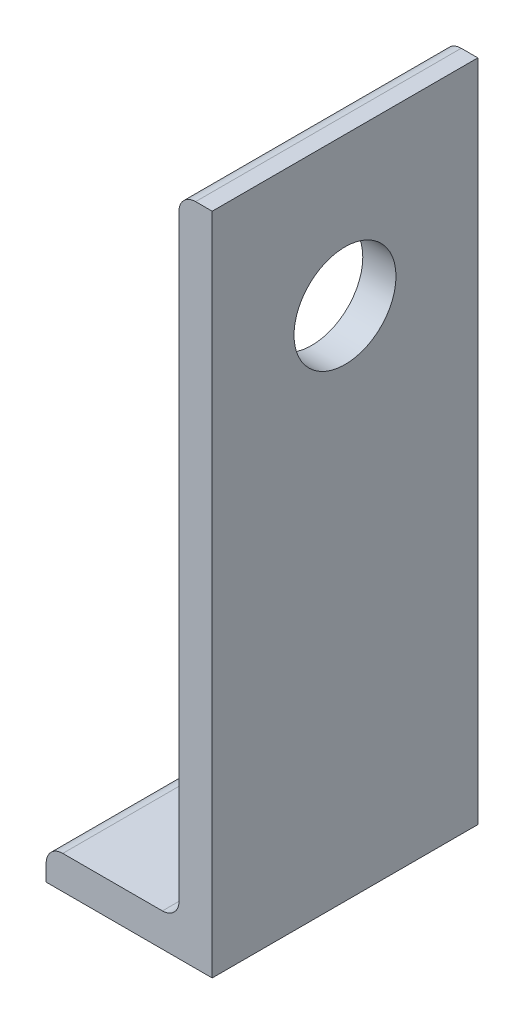
SolidWorks part; units mm, degrees
ref_plane "Front Plane" through (0, 0, 0) normal (0, 0, 1) x (1, 0, 0)
ref_plane "Top Plane" through (0, 0, 0) normal (0, 1, 0) x (1, 0, 0)
ref_plane "Right Plane" through (0, 0, 0) normal (1, 0, 0) x (0, 0, -1)
sketch "Sketch2" plane through (0, 0, 0) normal (0, 0, 1) x (1, 0, 0)
  line L0 (-15.875, 0) -> (15.875, 0)
  line L1 (15.875, 0) -> (15.875, 127)
  line L2 (15.875, 127) -> (9.525, 127) construction
  line L3 (9.525, 123.825) -> (9.525, 9.525)
  line L4 (6.35, 6.35) -> (-12.7, 6.35)
  line L5 (-15.875, 0) -> (-15.875, 6.35) construction
  line L6 (12.7, 127) -> (15.875, 127)
  line L7 (-15.875, 3.175) -> (-15.875, 0)
  arc A0 (9.525, 123.825) -> (12.7, 127) centre (12.7, 123.825) cw
  arc A1 (-15.875, 3.175) -> (-12.7, 6.35) centre (-12.7, 3.175) cw
  arc A2 (9.525, 9.525) -> (6.35, 6.35) centre (6.35, 9.525) cw
  dimension "Vert" = 127
  dimension "Horz" = 31.75
  dimension "Thickness" = 6.35
extrude "Boss-Extrude1" add sketch "Sketch2" along normal mid plane 50.8
ref_plane "Contact Plane 1" through (0, 6.35, 0) normal (0, 1, 0) x (1, 0, 0)
ref_plane "Contact Plane 2" through (9.525, 0, 0) normal (-1, 0, 0) x (0, 0, 1)
sketch "Sketch3" plane through (0, 0, 0) normal (0, -1, 0) x (1, 0, 0)
  line L0 (15.875, 0) -> (-15.875, 0) construction
  line L1 (15.875, 25.4) -> (15.875, -25.4) construction
  line L2 (-15.875, 25.4) -> (-15.875, -25.4) construction
  circle A0 centre (-4.826, 0) radius 4.765
  dimension "D1" = 9.53
  dimension "D2" = 20.701
extrude "Cut-Extrude1" cut sketch "Sketch3" against normal through all contours A0
sketch "Sketch4" plane through (15.875, 0, 0) normal (1, 0, 0) x (0, 0, -1)
  line L0 (-25.4, 0) -> (-25.4, 127) construction
  circle A1 centre (0, 98.65) radius 9.75
  dimension "D1" = 25.4
  dimension "D2" = 19.5
  dimension "D3" = 98.65
extrude "Cut-Extrude2" cut sketch "Sketch4" against normal blind 12.7
